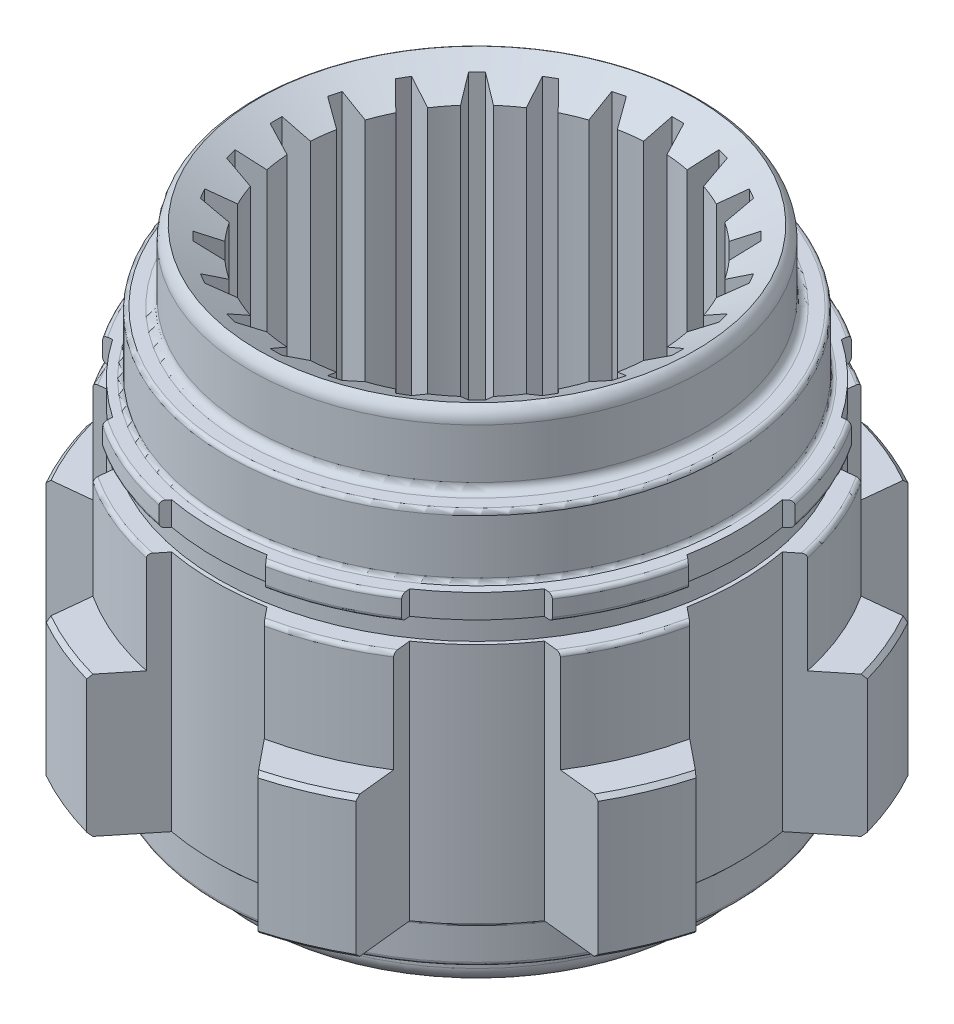
SolidWorks part; units mm, degrees
ref_plane "Plano frontal" through (0, 0, 0) normal (0, 0, 1) x (1, 0, 0)
ref_plane "Plano superior" through (0, 0, 0) normal (0, 1, 0) x (1, 0, 0)
ref_plane "Plano direito" through (0, 0, 0) normal (1, 0, 0) x (0, 0, -1)
sketch "Esboço1" plane through (0, 0, 0) normal (0, 0, 1) x (1, 0, 0)
  line L0 (0, -54.4613) -> (0, 50.8185) construction
  line L1 (22.5, 50.8185) -> (28.5, 50.8185)
  line L2 (28.5, 50.8185) -> (28.5, 41.8185)
  line L3 (28.5, 41.8185) -> (31.5, 41.8185)
  line L4 (31.5, 41.8185) -> (31.5, 34.0185)
  line L5 (31.5, 34.0185) -> (34, 34.0185)
  line L6 (34, 34.0185) -> (34, 31.0185)
  line L7 (34, 31.0185) -> (32.5, 31.0185)
  line L8 (32.5, 31.0185) -> (32.5, 28.3185)
  line L9 (32.5, 28.3185) -> (35, 28.3185)
  line L10 (35, 28.3185) -> (35, 15.5185)
  line L11 (35, 15.5185) -> (39.85, 15.5185)
  line L12 (39.85, 15.5185) -> (39.85, -2.1815)
  line L13 (39.85, -2.1815) -> (32.5, -2.1815)
  line L14 (32.5, -2.1815) -> (32.5, -7.1815)
  line L15 (32.5, -7.1815) -> (28.5, -7.1815)
  line L16 (28.5, -7.1815) -> (28.5, -12.1815)
  line L17 (28.5, -12.1815) -> (22.5, -12.1815)
  line L18 (22.5, -12.1815) -> (22.5, 50.8185)
  dimension "D1" = 22.5
  dimension "D2" = 28.5
  dimension "D3" = 31.5
  dimension "D4" = 34
  dimension "D5" = 32.5
  dimension "D6" = 35
  dimension "D7" = 39.85
  dimension "D8" = 32.5
  dimension "D9" = 28.5
  dimension "D10" = 5
  dimension "D11" = 5
  dimension "D12" = 17.7
  dimension "D13" = 3
  dimension "D14" = 2.7
  dimension "D15" = 18.5
  dimension "D16" = 7.8
  dimension "D17" = 63
revolve "Revolução1" add sketch "Esboço1" angle 360 about L0
chamfer "Chamfer1" distance 5 angle 30 2 edges at (0, -12.1815, -22.5) (0, 50.8185, -22.5)
sketch "Sketch1" plane through (0, 50.8185, 0) normal (0, 1, 0) x (1, 0, 0)
  line L0 (0, 0) -> (-52.3995, 0) construction
  line L1 (0, 0) -> (0, 22.5) construction
  line L2 (-1.5, 22.3214) -> (1.5, 22.3214)
  line L3 (-0.75, 25.3) -> (0.75, 25.3)
  line L4 (4.3283, 21.9491) -> (7.2261, 21.1726)
  line L5 (5.8237, 24.632) -> (7.2726, 24.2438)
  line L6 (-1.5, 22.3214) -> (-0.75, 25.3)
  line L7 (0.75, 25.3) -> (1.5, 22.3214)
  line L8 (4.3283, 21.9491) -> (5.8237, 24.632)
  line L9 (7.2726, 24.2438) -> (7.2261, 21.1726)
  line L10 (9.8617, 20.0809) -> (12.4598, 18.5809)
  line L11 (12.0005, 22.2854) -> (13.2995, 21.5354)
  line L12 (9.8617, 20.0809) -> (12.0005, 22.2854)
  line L13 (13.2995, 21.5354) -> (12.4598, 18.5809)
  line L14 (14.723, 16.8443) -> (16.8443, 14.723)
  line L15 (17.3595, 18.4201) -> (18.4201, 17.3595)
  line L16 (14.723, 16.8443) -> (17.3595, 18.4201)
  line L17 (18.4201, 17.3595) -> (16.8443, 14.723)
  line L18 (18.5809, 12.4598) -> (20.0809, 9.8617)
  line L19 (21.5354, 13.2995) -> (22.2854, 12.0005)
  line L20 (18.5809, 12.4598) -> (21.5354, 13.2995)
  line L21 (22.2854, 12.0005) -> (20.0809, 9.8617)
  line L22 (21.1726, 7.2261) -> (21.9491, 4.3283)
  line L23 (24.2438, 7.2726) -> (24.632, 5.8237)
  line L24 (21.1726, 7.2261) -> (24.2438, 7.2726)
  line L25 (24.632, 5.8237) -> (21.9491, 4.3283)
  line L26 (22.3214, 1.5) -> (22.3214, -1.5)
  line L27 (25.3, 0.75) -> (25.3, -0.75)
  line L28 (22.3214, 1.5) -> (25.3, 0.75)
  line L29 (25.3, -0.75) -> (22.3214, -1.5)
  line L30 (21.9491, -4.3283) -> (21.1726, -7.2261)
  line L31 (24.632, -5.8237) -> (24.2438, -7.2726)
  line L32 (21.9491, -4.3283) -> (24.632, -5.8237)
  line L33 (24.2438, -7.2726) -> (21.1726, -7.2261)
  line L34 (20.0809, -9.8617) -> (18.5809, -12.4598)
  line L35 (22.2854, -12.0005) -> (21.5354, -13.2995)
  line L36 (20.0809, -9.8617) -> (22.2854, -12.0005)
  line L37 (21.5354, -13.2995) -> (18.5809, -12.4598)
  line L38 (16.8443, -14.723) -> (14.723, -16.8443)
  line L39 (18.4201, -17.3595) -> (17.3595, -18.4201)
  line L40 (16.8443, -14.723) -> (18.4201, -17.3595)
  line L41 (17.3595, -18.4201) -> (14.723, -16.8443)
  line L42 (12.4598, -18.5809) -> (9.8617, -20.0809)
  line L43 (13.2995, -21.5354) -> (12.0005, -22.2854)
  line L44 (12.4598, -18.5809) -> (13.2995, -21.5354)
  line L45 (12.0005, -22.2854) -> (9.8617, -20.0809)
  line L46 (7.2261, -21.1726) -> (4.3283, -21.9491)
  line L47 (7.2726, -24.2438) -> (5.8237, -24.632)
  line L48 (7.2261, -21.1726) -> (7.2726, -24.2438)
  line L49 (5.8237, -24.632) -> (4.3283, -21.9491)
  line L50 (1.5, -22.3214) -> (-1.5, -22.3214)
  line L51 (0.75, -25.3) -> (-0.75, -25.3)
  line L52 (1.5, -22.3214) -> (0.75, -25.3)
  line L53 (-0.75, -25.3) -> (-1.5, -22.3214)
  line L54 (-4.3283, -21.9491) -> (-7.2261, -21.1726)
  line L55 (-5.8237, -24.632) -> (-7.2726, -24.2438)
  line L56 (-4.3283, -21.9491) -> (-5.8237, -24.632)
  line L57 (-7.2726, -24.2438) -> (-7.2261, -21.1726)
  line L58 (-9.8617, -20.0809) -> (-12.4598, -18.5809)
  line L59 (-12.0005, -22.2854) -> (-13.2995, -21.5354)
  line L60 (-9.8617, -20.0809) -> (-12.0005, -22.2854)
  line L61 (-13.2995, -21.5354) -> (-12.4598, -18.5809)
  line L62 (-14.723, -16.8443) -> (-16.8443, -14.723)
  line L63 (-17.3595, -18.4201) -> (-18.4201, -17.3595)
  line L64 (-14.723, -16.8443) -> (-17.3595, -18.4201)
  line L65 (-18.4201, -17.3595) -> (-16.8443, -14.723)
  line L66 (-18.5809, -12.4598) -> (-20.0809, -9.8617)
  line L67 (-21.5354, -13.2995) -> (-22.2854, -12.0005)
  line L68 (-18.5809, -12.4598) -> (-21.5354, -13.2995)
  line L69 (-22.2854, -12.0005) -> (-20.0809, -9.8617)
  line L70 (-21.1726, -7.2261) -> (-21.9491, -4.3283)
  line L71 (-24.2438, -7.2726) -> (-24.632, -5.8237)
  line L72 (-21.1726, -7.2261) -> (-24.2438, -7.2726)
  line L73 (-24.632, -5.8237) -> (-21.9491, -4.3283)
  line L74 (-22.3214, -1.5) -> (-22.3214, 1.5)
  line L75 (-25.3, -0.75) -> (-25.3, 0.75)
  line L76 (-22.3214, -1.5) -> (-25.3, -0.75)
  line L77 (-25.3, 0.75) -> (-22.3214, 1.5)
  line L78 (-21.9491, 4.3283) -> (-21.1726, 7.2261)
  line L79 (-24.632, 5.8237) -> (-24.2438, 7.2726)
  line L80 (-21.9491, 4.3283) -> (-24.632, 5.8237)
  line L81 (-24.2438, 7.2726) -> (-21.1726, 7.2261)
  line L82 (-20.0809, 9.8617) -> (-18.5809, 12.4598)
  line L83 (-22.2854, 12.0005) -> (-21.5354, 13.2995)
  line L84 (-20.0809, 9.8617) -> (-22.2854, 12.0005)
  line L85 (-21.5354, 13.2995) -> (-18.5809, 12.4598)
  line L86 (-16.8443, 14.723) -> (-14.723, 16.8443)
  line L87 (-18.4201, 17.3595) -> (-17.3595, 18.4201)
  line L88 (-16.8443, 14.723) -> (-18.4201, 17.3595)
  line L89 (-17.3595, 18.4201) -> (-14.723, 16.8443)
  line L90 (-12.4598, 18.5809) -> (-9.8617, 20.0809)
  line L91 (-13.2995, 21.5354) -> (-12.0005, 22.2854)
  line L92 (-12.4598, 18.5809) -> (-13.2995, 21.5354)
  line L93 (-12.0005, 22.2854) -> (-9.8617, 20.0809)
  line L94 (-7.2261, 21.1726) -> (-4.3283, 21.9491)
  line L95 (-7.2726, 24.2438) -> (-5.8237, 24.632)
  line L96 (-7.2261, 21.1726) -> (-7.2726, 24.2438)
  line L97 (-5.8237, 24.632) -> (-4.3283, 21.9491)
  circle A1 centre (0, 0) radius 22.5 construction
  point P81 (0, 0)
  dimension "D1" = 24
extrude "Cut-Extrude1" cut sketch "Sketch1" against normal blind 80
fillet "Filete1" radius 2 1 edges at (0, 50.8185, -28.5)
fillet "Filete2" radius 1 1 edges at (0, 41.8185, -28.5)
fillet "Filete3" radius 0.5 5 edges at (0, 28.3185, -35) (0, 31.0185, -34) (0, 34.0185, -34) (0, 34.0185, -31.5) (0, 41.8185, -31.5)
chamfer "Chanfro1" distance 0.5 angle 45 2 edges at (0, -2.1815, -39.85) (0, 15.5185, -39.85)
fillet "Filete4" radius 2 1 edges at (0, -12.1815, -28.5)
fillet "Filete5" radius 0.5 3 edges at (0, -2.1815, -32.5) (0, -7.1815, -32.5) (0, -7.1815, -28.5)
sketch "Esboço2" plane through (0, -12.1815, 0) normal (0, -1, 0) x (1, 0, 0)
  line L0 (-6, -32.45) -> (-13.6971, -41.9551)
  line L1 (6, -32.45) -> (13.6971, -41.9551)
  line L2 (0, 0) -> (0, -41.6775) construction
  line L3 (-13.6971, -41.9551) -> (13.6971, -41.9551)
  line L4 (13.6971, -41.9551) -> (14.0281, -41.8701)
  line L5 (-27.1882, -18.7029) -> (-39.3521, -19.9814)
  line L6 (-18.7029, -27.1882) -> (-19.9814, -39.3521)
  line L7 (-39.3521, -19.9814) -> (-19.9814, -39.3521)
  line L8 (-19.9814, -39.3521) -> (-19.6873, -39.526)
  line L9 (-32.45, 6) -> (-41.9551, 13.6971)
  line L10 (-32.45, -6) -> (-41.9551, -13.6971)
  line L11 (-41.9551, 13.6971) -> (-41.9551, -13.6971)
  line L12 (-41.9551, -13.6971) -> (-41.8701, -14.0281)
  line L13 (-18.7029, 27.1882) -> (-19.9814, 39.3521)
  line L14 (-27.1882, 18.7029) -> (-39.3521, 19.9814)
  line L15 (-19.9814, 39.3521) -> (-39.3521, 19.9814)
  line L16 (-39.3521, 19.9814) -> (-39.526, 19.6873)
  line L17 (6, 32.45) -> (13.6971, 41.9551)
  line L18 (-6, 32.45) -> (-13.6971, 41.9551)
  line L19 (13.6971, 41.9551) -> (-13.6971, 41.9551)
  line L20 (-13.6971, 41.9551) -> (-14.0281, 41.8701)
  line L21 (27.1882, 18.7029) -> (39.3521, 19.9814)
  line L22 (18.7029, 27.1882) -> (19.9814, 39.3521)
  line L23 (39.3521, 19.9814) -> (19.9814, 39.3521)
  line L24 (19.9814, 39.3521) -> (19.6873, 39.526)
  line L25 (32.45, -6) -> (41.9551, -13.6971)
  line L26 (32.45, 6) -> (41.9551, 13.6971)
  line L27 (41.9551, -13.6971) -> (41.9551, 13.6971)
  line L28 (41.9551, 13.6971) -> (41.8701, 14.0281)
  line L29 (18.7029, -27.1882) -> (19.9814, -39.3521)
  line L30 (27.1882, -18.7029) -> (39.3521, -19.9814)
  line L31 (19.9814, -39.3521) -> (39.3521, -19.9814)
  line L32 (39.3521, -19.9814) -> (39.526, -19.6873)
  arc A0 (-27.1882, -18.7029) -> (-18.7029, -27.1882) centre (0, 0) ccw
  arc A1 (-6, -32.45) -> (6, -32.45) centre (0, 0) ccw
  arc A2 (-32.45, 6) -> (-32.45, -6) centre (0, 0) ccw
  arc A3 (-18.7029, 27.1882) -> (-27.1882, 18.7029) centre (0, 0) ccw
  arc A4 (6, 32.45) -> (-6, 32.45) centre (0, 0) ccw
  arc A5 (27.1882, 18.7029) -> (18.7029, 27.1882) centre (0, 0) ccw
  arc A6 (32.45, -6) -> (32.45, 6) centre (0, 0) ccw
  arc A7 (18.7029, -27.1882) -> (27.1882, -18.7029) centre (0, 0) ccw
  dimension "D1" = 78
  dimension "D2" = 8
extrude "Corte-extrusão1" cut sketch "Esboço2" against normal through all
